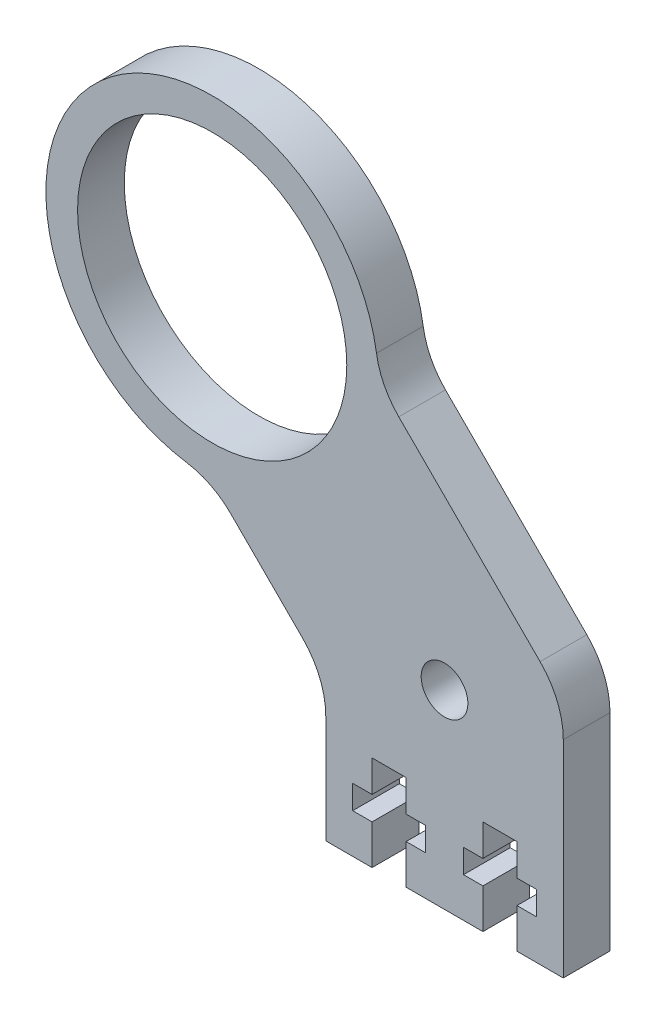
SolidWorks part; units mm, degrees
ref_plane "Front Plane" through (0, 0, 0) normal (0, 0, 1) x (1, 0, 0)
ref_plane "Top Plane" through (0, 0, 0) normal (0, 1, 0) x (1, 0, 0)
ref_plane "Right Plane" through (0, 0, 0) normal (1, 0, 0) x (0, 0, -1)
sketch "Sketch1" plane through (0, 0, 0) normal (0, 0, 1) x (1, 0, 0)
  line L0 (0, 0) -> (-29.3449, 29.3449) construction
  line L1 (0, 0) -> (0, 31.0325) construction
  line L2 (-15, -6.2132) -> (-15, -24)
  line L3 (-15, -24) -> (15, -24)
  line L4 (15, -24) -> (15, 6.2132)
  line L5 (0, 0) -> (0, -24) construction
  line L6 (15, 6.2132) -> (-8.346, 29.5592)
  line L7 (-15, -6.2132) -> (-29.5592, 8.346)
  line L8 (10.6066, 10.6066) -> (-18.7383, 39.9515) construction
  line L9 (-10.6066, -10.6066) -> (-39.9515, 18.7383) construction
  circle A0 centre (0, 0) radius 2.95
  arc A1 (-8.346, 29.5592) -> (-29.5592, 8.346) centre (-29.3449, 29.3449) ccw
  dimension "D1" = 5.9
  dimension "D3" = 42
  dimension "D2" = 41.5
  dimension "D4" = 45
  dimension "D5" = 24
  dimension "D6" = 30
  dimension "D7" = 15
  dimension "D8" = 15
extrude "Boss-Extrude1" add sketch "Sketch1" along normal blind 5.9
sketch "Sketch2" plane through (0, 0, 5.9) normal (0, 0, 1) x (1, 0, 0)
  circle A0 centre (-29.3449, 29.3449) radius 17
  dimension "D1" = 34
extrude "Cut-Extrude1" cut sketch "Sketch2" against normal through all
sketch "Sketch3" plane through (0, 0, 5.9) normal (0, 0, 1) x (1, 0, 0)
  line L0 (-15, -24) -> (15, -24) construction
  line L1 (-9.15, -24) -> (-4.85, -24)
  line L2 (-9.15, -24) -> (-9.15, -19)
  line L3 (-9.15, -12) -> (-4.85, -12)
  line L4 (-4.85, -24) -> (-4.85, -19)
  line L5 (0, 0) -> (0, -24) construction
  line L6 (-4.85, -16) -> (-2.4, -16)
  line L7 (-11.6, -16) -> (-9.15, -16)
  line L8 (-11.6, -16) -> (-11.6, -19)
  line L9 (-11.6, -19) -> (-9.15, -19)
  line L10 (-2.4, -16) -> (-2.4, -19)
  line L11 (-9.15, -16) -> (-9.15, -12)
  line L12 (-4.85, -19) -> (-2.4, -19)
  line L13 (-4.85, -16) -> (-4.85, -12)
  line L14 (4.85, -16) -> (4.85, -12)
  line L15 (4.85, -19) -> (2.4, -19)
  line L16 (9.15, -16) -> (9.15, -12)
  line L17 (2.4, -16) -> (2.4, -19)
  line L18 (11.6, -19) -> (9.15, -19)
  line L19 (11.6, -16) -> (11.6, -19)
  line L20 (11.6, -16) -> (9.15, -16)
  line L21 (4.85, -16) -> (2.4, -16)
  line L22 (4.85, -24) -> (4.85, -19)
  line L23 (9.15, -12) -> (4.85, -12)
  line L24 (9.15, -24) -> (9.15, -19)
  line L25 (9.15, -24) -> (4.85, -24)
  point P6 (-7, -12)
  point P18 (-10.375, -19)
  dimension "D1" = 4.3
  dimension "D2" = 7
  dimension "D3" = 12
  dimension "D4" = 9.2
  dimension "D5" = 3
  dimension "D6" = 5
extrude "Cut-Extrude2" cut sketch "Sketch3" against normal through all
fillet "Fillet1" radius 10 4 edges at (-15, -6.2132, 2.95) (15, 6.2132, 2.95) (-29.5592, 8.346, 2.95) (-8.346, 29.5592, 2.95)
equation "\"smallPulleyTeeth\"= 15"
equation "\"largePulleyTeeth\"= 30"
equation "\"eighthThick\"= 2.9mm"
equation "\"sixteenthThick\" = 1.7mm"
equation "\"quarterThick\"=5.9mm"
equation "\"OD\" = 145mm"
equation "\"puckAngle\" = 60.5deg"
equation "\"puckDiam\" = 76.5mm"
equation "\"axlePress\" = 5.9mm"
equation "\"D1@Sketch1\"=\"axlePress\""
equation "\"D1@Boss-Extrude1\"=\"quarterThick\""
equation "\"press\" = 0.2mm"
equation "\"wheelClear\" = 0.3mm"
equation "\"10-32clear\" = 4.5mm"
equation "\"D1@Sketch3\"=\"10-32clear\" - \"press\""
equation "\"6-32clear\" = 3.3mm"
equation "\"8-32clear\" = 4.0mm"
equation "\"wheelHeight\" = 24mm"
equation "\"D5@Sketch1\"=\"wheelHeight\""
